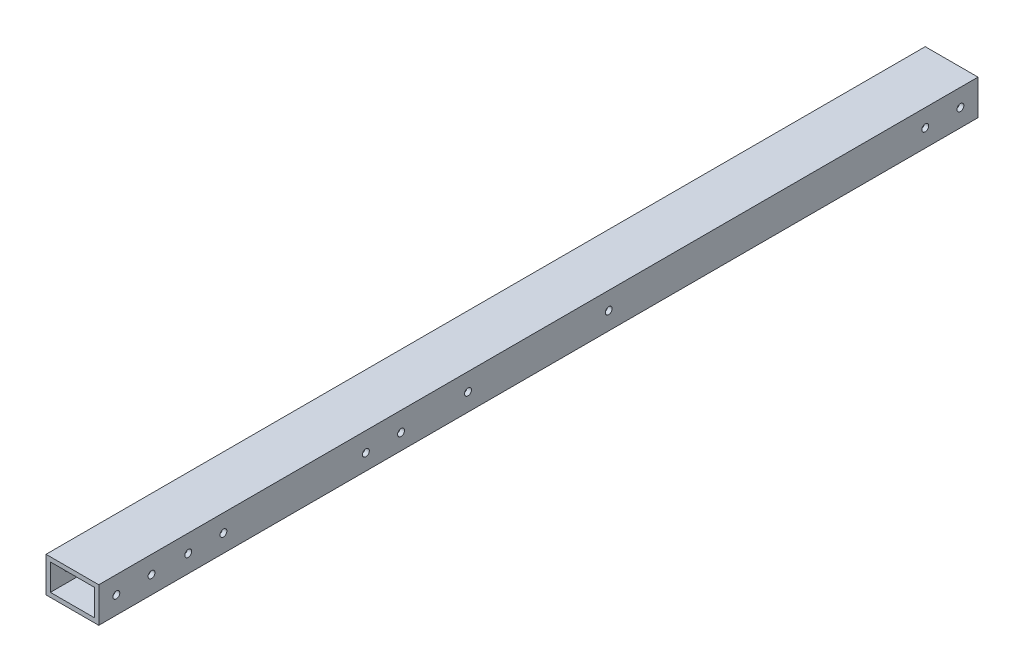
SolidWorks part; units mm, degrees
ref_plane "Front Plane" through (0, 0, 0) normal (0, 0, 1) x (1, 0, 0)
ref_plane "Top Plane" through (0, 0, 0) normal (0, 1, 0) x (1, 0, 0)
ref_plane "Right Plane" through (0, 0, 0) normal (1, 0, 0) x (0, 0, -1)
sketch "Sketch1" plane through (0, 0, 0) normal (0, 0, 1) x (1, 0, 0)
  line L0 (-15.875, 9.525) -> (15.875, 9.525)
  line L2 (-19.05, 12.7) -> (19.05, 12.7)
  line L3 (-19.05, 12.7) -> (-19.05, -12.7)
  line L4 (-19.05, -12.7) -> (19.05, -12.7)
  line L5 (19.05, 12.7) -> (19.05, -12.7)
  line L10 (15.875, 9.525) -> (15.875, -9.525)
  line L11 (-15.875, -9.525) -> (15.875, -9.525)
  line L12 (-15.875, 9.525) -> (-15.875, -9.525)
  point P12 (0, 12.7)
  point P14 (19.05, 0)
  dimension "Wall Thickness" = 3.175
  dimension "Outside Width" = 38.1
  dimension "Outside Height" = 25.4
  dimension "Inside Height" = 19.05
  dimension "Inside Width" = 31.75
sketch "Sketch2" plane through (0, 0, 0) normal (1, 0, 0) x (0, 0, -1)
  line L0 (317.5, 0) -> (-317.5, 0)
  point P4 (0, 0)
  point P7 (-317.5, 0)
  point P10 (317.5, 0)
  dimension "Length" = 635
sketch "Sketch3" plane through (0, 0, 0) normal (0, 0, 1) x (1, 0, 0)
  line L21 (19.05, 12.7) -> (-19.05, 12.7)
  line L22 (19.05, -12.7) -> (19.05, 12.7)
  line L23 (-19.05, -12.7) -> (19.05, -12.7)
  line L24 (-19.05, 12.7) -> (-19.05, -12.7)
  line L25 (19.05, 12.7) -> (-19.05, 12.7)
  line L26 (19.05, -12.7) -> (19.05, 12.7)
  line L27 (-19.05, -12.7) -> (19.05, -12.7)
  line L28 (-19.05, 12.7) -> (-19.05, -12.7)
  line L29 (15.875, 9.525) -> (-15.875, 9.525)
  line L30 (15.875, -9.525) -> (15.875, 9.525)
  line L31 (-15.875, -9.525) -> (15.875, -9.525)
  line L32 (-15.875, 9.525) -> (-15.875, -9.525)
  line L33 (15.875, 9.525) -> (-15.875, 9.525)
  line L34 (15.875, -9.525) -> (15.875, 9.525)
  line L35 (-15.875, -9.525) -> (15.875, -9.525)
  line L36 (-15.875, 9.525) -> (-15.875, -9.525)
  dimension "D1" = 0
  dimension "D2" = 0
extrude "Boss-Extrude1" add sketch "Sketch3" along normal up to vertex (317.5 mm away) and the other way up to vertex (317.5 mm away) up to point (0, 0, 317.5) other way up to point (0, 0, -317.5)
sketch "Drawing Reference" plane through (0, 0, 0) normal (1, 0, 0) x (0, 0, -1)
  line L0 (-317.5, 0) -> (317.5, 0) construction
  line L1 (0, -12.7) -> (0, 12.7) construction
  line L2 (-317.5, -12.7) -> (317.5, -12.7) construction
  line L5 (-317.5, 12.7) -> (317.5, 12.7) construction
  point P7 (-290.068, 0)
  point P8 (290.068, 0)
  dimension "D1" = 27.432
sketch "Sketch4" plane through (-19.05, 0, 0) normal (-1, 0, 0) x (0, 0, 1)
  line L0 (-317.5, 0) -> (-304.8, 0)
  line L1 (-317.5, 12.7) -> (-317.5, -12.7) construction
  line L2 (-304.8, 0) -> (-279.4, 0)
  line L3 (317.5, 12.7) -> (317.5, -12.7) construction
  line L4 (317.5, 0) -> (304.8, 0)
  line L5 (304.8, 0) -> (279.4, 0)
  line L6 (0, 0) -> (50.8, 0) construction
  line L7 (0, 0) -> (-50.8, 0) construction
  point P11 (-304.8, 0)
  point P13 (-279.4, 0)
  point P14 (304.8, 0)
  point P15 (279.4, 0)
hole_wizard "#10 Clearance Hole2" positions "Sketch11" profile "Sketch12" hole size "#10" standard "ANSI Inch" end condition through all
sketch "Sketch11" plane through (-19.05, 0, 0) normal (-1, 0, 0) x (0, 0, 1)
  point P0 (-304.8, 0)
  point P3 (-279.4, 0)
  point P6 (279.4, 0)
  point P9 (304.8, 0)
sketch "Sketch12" plane through (-19.05, 0, -304.8) normal (0, 1, 0) x (0, 0, 1)
  line L0 (0, 0) -> (0, 38.1)
  line L1 (0, 38.1) -> (2.4892, 38.1)
  line L2 (2.4892, 38.1) -> (2.4892, 0)
  line L5 (2.4892, 0) -> (0, 0)
  line L11 (0, -6.35) -> (0, 107.95) construction
  dimension "Thru Hole Dia." = 4.9784
  dimension "Thru Hole Depth" = 38.1
hole_wizard "#10 Clearance Hole5" positions "Sketch14" profile "Sketch16" hole size "#10" standard "ANSI Inch" end condition through all
sketch "Sketch14" plane through (19.05, 0, 0) normal (1, 0, 0) x (0, 0, -1)
  point P10 (-124.587, -1.2316)
  point P13 (-99.187, -1.2316)
  point P17 (-252.857, 0)
  point P20 (-227.457, 0)
sketch "Sketch16" plane through (19.05, -1.2316, 124.587) normal (0, 1, 0) x (0, 0, -1)
  line L0 (0, 0) -> (0, 38.1)
  line L1 (0, 38.1) -> (2.4892, 38.1)
  line L2 (2.4892, 38.1) -> (2.4892, 0)
  line L5 (2.4892, 0) -> (0, 0)
  line L11 (0, -6.35) -> (0, 107.95) construction
  dimension "Thru Hole Dia." = 4.9784
  dimension "Thru Hole Depth" = 38.1
sketch "Sketch17" plane through (19.05, 0, 0) normal (1, 0, 0) x (0, 0, -1)
  point P0 (-252.857, 0)
  point P1 (-227.457, 0)
hole_wizard "#10 Clearance Hole4" positions "Sketch18" profile "Sketch19" hole size "#10" standard "ANSI Inch" end condition through all
sketch "Sketch18" plane through (19.05, 0, 0) normal (1, 0, 0) x (0, 0, -1)
  point P0 (-252.857, 0)
  point P3 (-227.457, 0)
sketch "Sketch19" plane through (19.05, 0, 252.857) normal (0, 1, 0) x (0, 0, -1)
  line L0 (0, 0) -> (0, 38.1)
  line L1 (0, 38.1) -> (2.4892, 38.1)
  line L2 (2.4892, 38.1) -> (2.4892, 0)
  line L5 (2.4892, 0) -> (0, 0)
  line L11 (0, -6.35) -> (0, 107.95) construction
  dimension "Thru Hole Dia." = 4.9784
  dimension "Thru Hole Depth" = 38.1
hole_wizard "#10 Clearance Hole3" positions "Sketch20" profile "Sketch21" hole size "#10" standard "ANSI Inch" end condition through all
sketch "Sketch20" plane through (-19.05, 0, 0) normal (-1, 0, 0) x (0, 0, 1)
  point P0 (-50.8, 0)
  point P3 (50.8, 0)
sketch "Sketch21" plane through (-19.05, 0, -50.8) normal (0, 1, 0) x (0, 0, 1)
  line L0 (0, 0) -> (0, 38.1)
  line L1 (0, 38.1) -> (2.4892, 38.1)
  line L2 (2.4892, 38.1) -> (2.4892, 0)
  line L5 (2.4892, 0) -> (0, 0)
  line L11 (0, -6.35) -> (0, 107.95) construction
  dimension "Thru Hole Dia." = 4.9784
  dimension "Thru Hole Depth" = 38.1
equation "\"D1@Drawing Reference\"=\"Outside Width@Sketch1\" * 0.72"
